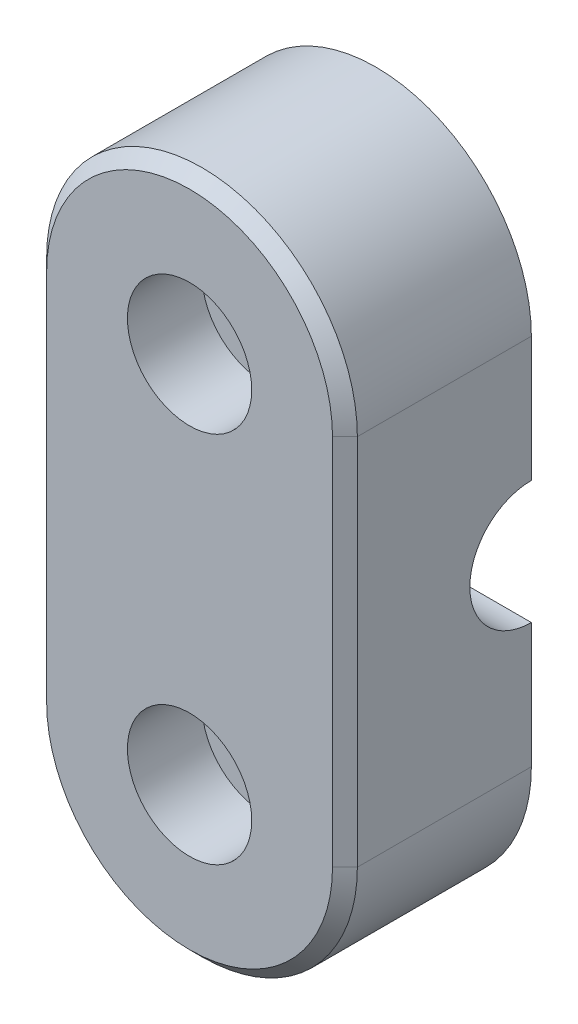
SolidWorks part; units mm, degrees
ref_plane "Front Plane" through (0, 0, 0) normal (0, 0, 1) x (1, 0, 0)
ref_plane "Top Plane" through (0, 0, 0) normal (0, 1, 0) x (1, 0, 0)
ref_plane "Right Plane" through (0, 0, 0) normal (1, 0, 0) x (0, 0, -1)
sketch "Sketch1" plane through (0, 0, 0) normal (0, 0, 1) x (1, 0, 0)
  line L12 (-12.5, 15) -> (-12.5, -15)
  line L13 (12.5, 15) -> (12.5, -15)
  arc A0 (12.5, 15) -> (-12.5, 15) centre (0, 15) ccw construction
  arc A1 (-12.5, -15) -> (12.5, -15) centre (0, -15) ccw construction
  arc A2 (12.5, 15) -> (-12.5, 15) centre (0, 15) ccw
  arc A3 (-12.5, -15) -> (12.5, -15) centre (0, -15) ccw
  circle A4 centre (0, 15) radius 3.25 construction
  circle A5 centre (0, -15) radius 3.25 construction
  circle A6 centre (0, 15) radius 3.25
  circle A7 centre (0, -15) radius 3.25
extrude "Boss-Extrude1" add sketch "Sketch1" along normal blind 15 contours A3 A7 | A2 A6 region at (0, 0, 0)
sketch "Sketch2" plane through (12.5, 0, 0) normal (1, 0, 0) x (0, 0, -1)
  circle A0 centre (0, 0) radius 4.95
  arc A2 (0, -4.95) -> (0, 4.95) centre (0, 0) ccw construction
extrude "Cut-Extrude1" cut sketch "Sketch2" against normal up to next
chamfer "Chamfer1" distance 1 angle 45 4 edges at (0, -27.5, 15) (0, 27.5, 15) (-12.5, 0, 15) (12.5, 0, 15)
sketch "Sketch3" plane through (0, 0, 15) normal (0, 0, 1) x (1, 0, 0)
  circle A0 centre (0, 15) radius 5
  circle A1 centre (0, -15) radius 5
  dimension "D1" = 10
extrude "Cut-Extrude2" cut sketch "Sketch3" against normal blind 6
sketch "Sketch5" plane through (0, 0, 0) normal (1, 0, 0) x (0, 0, -1)
  line L0 (0, 4.95) -> (0, -4.95)
  circle A0 centre (0, 0) radius 4.95
  circle A1 centre (0, 0) radius 4.5
  arc A2 (0, -4.5) -> (0, 4.5) centre (0, 0) ccw construction
  arc A4 (0, 4.95) -> (0, -4.95) centre (0, 0) ccw construction
extrude "Boss-Extrude2" add sketch "Sketch5" along normal mid plane 1.9 contours A1 L0 A0 region at (0, 4.725, 0.1107)
